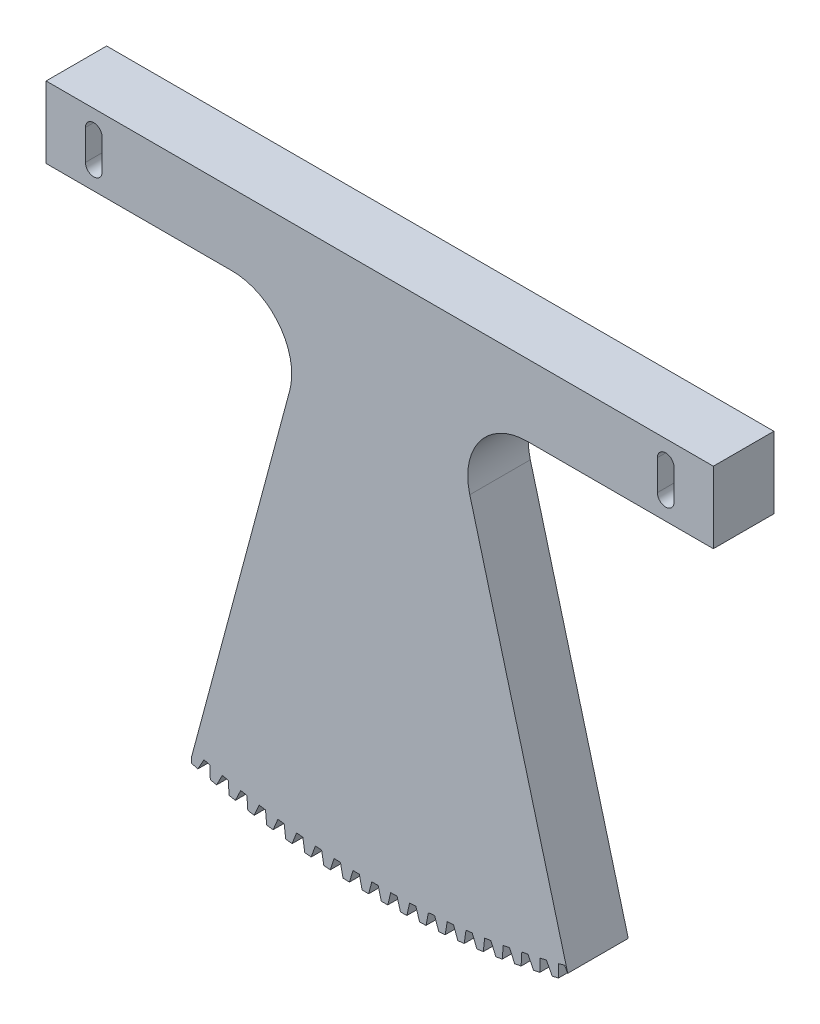
SolidWorks part; units mm, degrees
ref_plane "Front Plane" through (0, 0, 0) normal (0, 0, 1) x (1, 0, 0)
ref_plane "Top Plane" through (0, 0, 0) normal (0, 1, 0) x (1, 0, 0)
ref_plane "Right Plane" through (0, 0, 0) normal (1, 0, 0) x (0, 0, -1)
sketch "Sketch3" plane through (0, 0, 0) normal (0, 0, 1) x (1, 0, 0)
  line L0 (0, 0) -> (0, -304.8) construction
  line L1 (-21.234, -79.2464) -> (-78.888, -294.4142)
  line L2 (21.234, -79.2464) -> (78.888, -294.4142)
  line L4 (-140, -79.56) -> (140, -79.56)
  line L5 (-140, -79.56) -> (-140, -109.56)
  line L6 (-140, -109.56) -> (140, -109.56)
  line L7 (140, -79.56) -> (140, -109.56)
  line L8 (0, -109.56) -> (0, -79.56) construction
  line L9 (-140, -94.56) -> (140, -94.56) construction
  arc A0 (-78.888, -294.4142) -> (78.888, -294.4142) centre (0, 0) ccw
  point P269 (0, -94.56)
  dimension "D1" = 304.8
  dimension "D4" = 79.56
  dimension "D5" = 30
  dimension "D6" = 280
  dimension "D7" = 140
extrude "Boss-Extrude2" add sketch "Sketch3" along normal blind 25.4 contours L7 L4 L2 L6 | L1 L6 L2 L4 | L1 L4 L2 | L5 L6 L1 L4 | L1 A0 L2 L6 region at (0, -95.3531, 0) region at (-82.6452, -94.3847, 0) region at (0, -220.3694, 0) region at (82.6452, -94.3847, 0)
fillet "Fillet1" radius 25 2 edges at (-29.3565, -109.56, 12.7) (29.3565, -109.56, 12.7)
sketch "Sketch4" plane through (0, -79.56, 0) normal (0, 1, 0) x (1, 0, 0)
  line L1 (-140, 0) -> (140, 0)
  line L2 (-140, 0) -> (-140, -25.4)
  line L3 (-140, -25.4) -> (140, -25.4)
  line L4 (140, 0) -> (140, -25.4)
  line L5 (0, -25.4) -> (0, 0) construction
  line L6 (-140, -12.7) -> (140, -12.7) construction
  point P252 (0, -12.7)
sketch "Sketch5" plane through (0, 0, 0) normal (0, 0, -1) x (-1, 0, 0)
  line L0 (-123.5, -94.56) -> (-123.5, -100.91)
  line L1 (-116.5, -94.56) -> (-116.5, -100.91)
  line L2 (116.5, -94.56) -> (116.5, -88.21)
  line L3 (140, -79.56) -> (-140, -79.56) construction
  line L4 (-120, -88.21) -> (-120, -100.91) construction
  line L5 (0, -79.56) -> (0, -109.56) construction
  line L6 (-116.5, -94.56) -> (-116.5, -88.21)
  line L7 (-123.5, -94.56) -> (-123.5, -88.21)
  line L8 (116.5, -94.56) -> (116.5, -100.91)
  line L9 (123.5, -94.56) -> (123.5, -100.91)
  line L10 (123.5, -94.56) -> (123.5, -88.21)
  line L11 (-140, -79.56) -> (-140, -109.56) construction
  line L12 (120, -88.21) -> (120, -100.91) construction
  arc A1 (-116.5, -88.21) -> (-123.5, -88.21) centre (-120, -88.21) ccw
  arc A2 (-123.5, -100.91) -> (-116.5, -100.91) centre (-120, -100.91) ccw
  arc A3 (123.5, -100.91) -> (116.5, -100.91) centre (120, -100.91) cw
  arc A4 (116.5, -88.21) -> (123.5, -88.21) centre (120, -88.21) cw
  dimension "D1" = 16.5
  dimension "D2" = 7
  dimension "D3" = 8.65
  dimension "D5" = 3.5
  dimension "D4" = 6.35
sketch "Sketch13" plane through (0, 0, 0) normal (0, 0, -1) x (-1, 0, 0)
  line L0 (0, 0) -> (78.888, -294.4142)
  line L1 (0, 0) -> (-78.888, -294.4142)
  arc A0 (-78.888, -294.4142) -> (78.888, -294.4142) centre (0, 0) ccw
  arc A1 (-78.888, -294.4142) -> (78.888, -294.4142) centre (0, 0) ccw construction
  arc A2 (-78.888, -294.4142) -> (78.888, -294.4142) centre (0, 0) ccw
  circle A3 centre (0, 0) radius 304.8
  dimension "D1" = 609.6
sketch "Sketch14" plane through (0, 0, 0) normal (0, 0, -1) x (-1, 0, 0)
  line L0 (0, 0) -> (80.0203, -298.6399) construction
  line L2 (78.888, -294.4142) -> (78.9109, -297.0369)
  line L3 (78.9109, -297.0369) -> (76.2891, -297.7211)
  line L18 (76.2891, -297.7211) -> (75.0275, -295.4216)
  line L20 (0, 0) -> (-79.2746, -295.8555) construction
  line L32 (78.888, -294.4142) -> (75.0275, -295.4216)
  line L33 (75.0275, -295.4216) -> (78.888, -294.4142)
  line L34 (0, 0) -> (-75.3952, -296.8678) construction
  line L35 (0, 0) -> (-71.5028, -297.8293) construction
  line L36 (0, 0) -> (-67.5982, -298.7397) construction
  line L37 (0, 0) -> (-63.6821, -299.5989) construction
  line L38 (0, 0) -> (-59.755, -300.4068) construction
  line L39 (0, 0) -> (-55.8176, -301.1633) construction
  line L40 (0, 0) -> (-51.8707, -301.8681) construction
  line L41 (0, 0) -> (-47.9149, -302.5212) construction
  line L42 (0, 0) -> (-43.951, -303.1225) construction
  line L43 (0, 0) -> (-39.9794, -303.6718) construction
  line L44 (0, 0) -> (-36.0011, -304.1691) construction
  line L45 (0, 0) -> (-32.0165, -304.6143) construction
  line L46 (0, 0) -> (-28.0265, -305.0073) construction
  line L47 (0, 0) -> (-24.0316, -305.348) construction
  line L48 (0, 0) -> (-20.0327, -305.6364) construction
  line L49 (0, 0) -> (-16.0303, -305.8724) construction
  line L50 (0, 0) -> (-12.0252, -306.0561) construction
  line L51 (0, 0) -> (-8.018, -306.1873) construction
  line L52 (0, 0) -> (-4.0094, -306.266) construction
  line L53 (0, 0) -> (-0.0002, -306.2922) construction
  line L54 (0, 0) -> (4.0091, -306.266) construction
  line L55 (0, 0) -> (8.0176, -306.1873) construction
  line L56 (0, 0) -> (12.0248, -306.0561) construction
  line L57 (0, 0) -> (16.03, -305.8725) construction
  line L58 (0, 0) -> (20.0323, -305.6364) construction
  line L59 (0, 0) -> (24.0313, -305.348) construction
  line L60 (0, 0) -> (28.0261, -305.0073) construction
  line L61 (0, 0) -> (32.0162, -304.6143) construction
  line L62 (0, 0) -> (36.0007, -304.1691) construction
  line L63 (0, 0) -> (39.9791, -303.6719) construction
  line L64 (0, 0) -> (43.9506, -303.1225) construction
  line L65 (0, 0) -> (47.9146, -302.5213) construction
  line L66 (0, 0) -> (51.8704, -301.8682) construction
  line L67 (0, 0) -> (55.8173, -301.1633) construction
  line L68 (0, 0) -> (59.7546, -300.4069) construction
  line L69 (0, 0) -> (63.6817, -299.599) construction
  line L70 (0, 0) -> (67.5979, -298.7398) construction
  line L71 (0, 0) -> (71.5025, -297.8293) construction
  line L72 (0, 0) -> (75.3948, -296.8679) construction
  line L73 (0, 0) -> (-79.2746, -295.8555) construction
  line L74 (0, 0) -> (-75.3952, -296.8678) construction
  line L137 (37.789, -141.0305) -> (78.888, -294.4142) construction
  line L138 (-140, -79.56) -> (-140, -109.56)
  line L139 (-140, -109.56) -> (-61.9371, -109.56)
  line L140 (-37.789, -141.0305) -> (-78.888, -294.4142)
  line L141 (78.888, -294.4142) -> (37.789, -141.0305)
  line L142 (61.9371, -109.56) -> (140, -109.56)
  line L143 (140, -109.56) -> (140, -79.56)
  line L144 (140, -79.56) -> (-140, -79.56)
  line L145 (-140, -79.56) -> (-140, -109.56)
  line L146 (-140, -109.56) -> (-61.9371, -109.56)
  line L147 (-37.789, -141.0305) -> (-78.888, -294.4142)
  line L149 (61.9371, -109.56) -> (140, -109.56)
  line L150 (140, -109.56) -> (140, -79.56)
  line L151 (140, -79.56) -> (-140, -79.56)
  circle A0 centre (0, 0) radius 307.34
  circle A1 centre (0, 0) radius 302.26
  arc A3 (-37.789, -141.0305) -> (-61.9371, -109.56) centre (-61.9371, -134.56) ccw
  arc A5 (61.9371, -109.56) -> (37.789, -141.0305) centre (61.9371, -134.56) ccw
  arc A6 (-37.789, -141.0305) -> (-61.9371, -109.56) centre (-61.9371, -134.56) ccw
  arc A8 (61.9371, -109.56) -> (37.789, -141.0305) centre (61.9371, -134.56) ccw
  arc A11 (-78.888, -294.4142) -> (78.888, -294.4142) centre (0, 0) ccw
  arc A12 (-78.888, -294.4142) -> (78.888, -294.4142) centre (0, 0) ccw
  arc M181 (-78.888, -294.4142) -> (78.888, -294.4142) centre (0, 0) ccw
  dimension "D5" = 614.68
  dimension "D6" = 30
  dimension "D7" = 40
  dimension "D4" = 604.52
  dimension "D1" = 14.5
  dimension "D3" = 14.5
  dimension "D8" = 0.75
  dimension "D9" = 306.2922
  dimension "D10" = 0.75
  dimension "D2" = 0
extrude "Boss-Extrude4" add sketch "Sketch14" against normal up to surface (25.4 mm away) contours L2 M181 region at (-77.2591, -296.0724, 0) up to face at (0, -146.6727, 25.4)
sketch "Sketch15" plane through (0, 0, 0) normal (1, 0, 0) x (0, 0, -1)
  line L0 (0, 0) -> (-23.3364, 0) construction
sketch "Sketch16" plane through (0, 0, 0) normal (0, 0, -1) x (-1, 0, 0)
  line L0 (75.0275, -295.4216) -> (73.7653, -293.1208)
  line L1 (73.7653, -293.1208) -> (71.1999, -293.7544)
  line L2 (71.1999, -293.7544) -> (71.1541, -296.3784)
  line L3 (0, 0) -> (71.5025, -297.8293) construction
  line L4 (0, 0) -> (75.3948, -296.8679) construction
  circle A0 centre (0, 0) radius 302.26 construction
  arc A1 (-78.888, -294.4142) -> (78.888, -294.4142) centre (0, 0) ccw construction
  dimension "D1" = 14.5
  dimension "D2" = 14.5
extrude "Cut-Extrude2" cut sketch "Sketch16" against normal through all and the other way through all
pattern_circular "CirPattern8" count 20 every 1.5 about axis through (0, 0, 0) along (0, 0, 1) of "Cut-Extrude2", "Boss-Extrude4"
extrude "Cut-Extrude3" cut sketch "Sketch5" against normal through all
equation "\"D7@Sketch3\"=\"D6@Sketch3\"/2"
